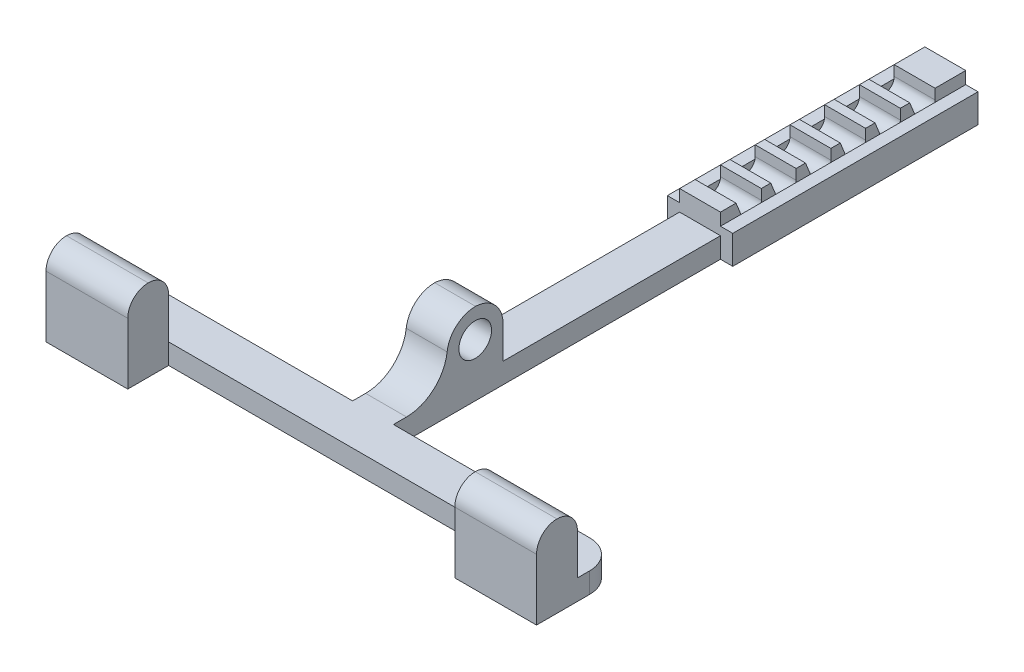
SolidWorks part; units mm, degrees
ref_plane "Front Plane" through (0, 0, 0) normal (0, 0, 1) x (1, 0, 0)
ref_plane "Top Plane" through (0, 0, 0) normal (0, 1, 0) x (1, 0, 0)
ref_plane "Right Plane" through (0, 0, 0) normal (1, 0, 0) x (0, 0, -1)
sketch "Sketch1" plane through (0, 0, 0) normal (0, 1, 0) x (1, 0, 0)
  line L0 (44.6675, -8.5158) -> (60, -8.5158)
  line L1 (0, 0) -> (0, 73.7509) construction
  line L2 (-5, 1.4842) -> (5, 1.4842)
  line L3 (-5, 1.4842) -> (5, 1.4842) construction
  line L4 (-5, 1.4842) -> (-5, 141.4842)
  line L5 (-5, 141.4842) -> (5, 141.4842)
  line L6 (5, 1.4842) -> (5, 141.4842)
  line L7 (-60, -8.5158) -> (44.6675, -8.5158)
  line L8 (-60, -8.5158) -> (-60, 1.4842)
  line L9 (-60, 1.4842) -> (60, 1.4842)
  line L10 (60, -8.5158) -> (60, 1.4842)
  line L11 (-60, -8.5158) -> (60, 1.4842) construction
  line L12 (-60, 1.4842) -> (60, -8.5158) construction
  line L13 (60, -8.5158) -> (40, -8.5158)
  line L14 (60, -8.5158) -> (60, -18.5158)
  line L15 (60, -18.5158) -> (40, -18.5158)
  line L16 (40, -8.5158) -> (40, -18.5158)
  line L17 (-60, -8.5158) -> (-40, -8.5158)
  line L18 (-60, -8.5158) -> (-60, -18.5158)
  line L19 (-60, -18.5158) -> (-40, -18.5158)
  line L20 (-40, -8.5158) -> (-40, -18.5158)
  line L21 (0, -55) -> (0, 55) construction
  line L22 (-5, 81.4842) -> (5, 81.4842)
  line L23 (-5, 28.2887) -> (5, 28.2887)
  line L24 (-5, 28.2887) -> (-5, 14.6797)
  line L25 (-5, 14.6797) -> (5, 14.6797)
  line L26 (5, 28.2887) -> (5, 14.6797)
  line L27 (-5, 28.2887) -> (5, 14.6797) construction
  line L28 (-5, 14.6797) -> (5, 28.2887) construction
  line L29 (5, 141.4842) -> (8, 141.4842)
  line L30 (5, 141.4842) -> (5, 81.4842)
  line L31 (5, 81.4842) -> (8, 81.4842)
  line L32 (8, 141.4842) -> (8, 81.4842)
  line L33 (-5, 141.4842) -> (-8, 141.4842)
  line L34 (-5, 141.4842) -> (-5, 81.4842)
  line L35 (-5, 81.4842) -> (-8, 81.4842)
  line L36 (-8, 141.4842) -> (-8, 81.4842)
  point P0 (0, 0)
  point P5 (0, 21.4842)
  point P6 (0, -3.5158)
  dimension "D1" = 10
  dimension "D2" = 120
  dimension "D3" = 30
  dimension "D4" = 20
  dimension "D5" = 120
  dimension "D6" = 3
  dimension "D7" = 60
extrude "Boss-Extrude1" add sketch "Sketch1" along normal blind 5 contours L7 L16 L15 L14 L0 | L0 L10 L9 L2 L8 L7 | L20 L7 L18 L19 | L25 L4 L2 L6 | L4 L25 L6 L23 | L4 L23 L6 L5 | L4 L23 L6 L22 region at (0, 0, 3.5158) region at (50, 0, 13.5158) region at (-50, 0, 13.5158) region at (0, 0, -8.082) region at (0, 0, -21.4842) region at (0, 0, -54.8865) region at (0, 0, -111.4842)
extrude "Boss-Extrude2" add sketch "Sketch1<3>" along normal blind 20 contours L20 L7 L18 L19 | L7 L16 L15 L14 L0 | L4 L25 L6 L23 region at (50, 0, 13.5158) region at (-50, 0, 13.5158) region at (0, 0, -21.4842)
sketch "Sketch1<3>" plane through (0, 0, 0) normal (0, 1, 0) x (1, 0, 0) same geometry as "Sketch1"
extrude "Boss-Extrude3" add sketch "Sketch1<5>" along normal blind 10 contours L4 L23 L6 L5 region at (0, 0, -111.4842)
sketch "Sketch1<5>" plane through (0, 0, 0) normal (0, 1, 0) x (1, 0, 0) same geometry as "Sketch1"
sketch "Sketch3" plane through (5, 0, 0) normal (1, 0, 0) x (0, 0, -1)
  line L0 (120.6636, 6.5701) -> (119.2891, 10)
  line L1 (81.4842, 10) -> (141.4842, 10) construction
  line L2 (133.9842, 7.5) -> (133.9842, 10)
  line L3 (129.1636, 6.5701) -> (127.7891, 10)
  line L4 (127.7891, 10) -> (133.9842, 10)
  line L5 (141.4842, 6) -> (139.9842, 4.5)
  line L6 (141.4842, 10) -> (141.4842, 0) construction
  line L7 (119.2891, 10) -> (125.4842, 10)
  line L8 (125.4842, 7.5) -> (125.4842, 10)
  line L9 (120.6636, 6.5701) -> (125.4842, 7.5) construction
  line L10 (112.1636, 6.5701) -> (110.7891, 10)
  line L11 (110.7891, 10) -> (116.9842, 10)
  line L12 (116.9842, 7.5) -> (116.9842, 10)
  line L13 (112.1636, 6.5701) -> (116.9842, 7.5) construction
  line L14 (103.6636, 6.5701) -> (102.2891, 10)
  line L15 (102.2891, 10) -> (108.4842, 10)
  line L16 (108.4842, 7.5) -> (108.4842, 10)
  line L17 (103.6636, 6.5701) -> (108.4842, 7.5) construction
  line L18 (95.1636, 6.5701) -> (93.7891, 10)
  line L19 (93.7891, 10) -> (99.9842, 10)
  line L20 (99.9842, 7.5) -> (99.9842, 10)
  line L21 (95.1636, 6.5701) -> (99.9842, 7.5) construction
  line L22 (86.6636, 6.5701) -> (85.2891, 10)
  line L23 (85.2891, 10) -> (91.4842, 10)
  line L24 (91.4842, 7.5) -> (91.4842, 10)
  line L25 (86.6636, 6.5701) -> (91.4842, 7.5) construction
  line L26 (139.9842, 4.5) -> (141.4842, 3)
  line L27 (141.4842, 3) -> (141.4842, 6)
  line L42 (21.4842, 20) -> (21.4842, 5.7881) construction
  line L43 (14.6797, 20) -> (28.2887, 20) construction
  line L44 (28.2887, 13) -> (14.6797, 13) construction
  arc A0 (129.1636, 6.5701) -> (133.9842, 7.5) centre (131.4842, 7.5) ccw
  arc A1 (120.6636, 6.5701) -> (125.4842, 7.5) centre (122.9842, 7.5) ccw
  arc A2 (112.1636, 6.5701) -> (116.9842, 7.5) centre (114.4842, 7.5) ccw
  arc A3 (103.6636, 6.5701) -> (108.4842, 7.5) centre (105.9842, 7.5) ccw
  arc A4 (95.1636, 6.5701) -> (99.9842, 7.5) centre (97.4842, 7.5) ccw
  arc A5 (86.6636, 6.5701) -> (91.4842, 7.5) centre (88.9842, 7.5) ccw
  circle A9 centre (21.4842, 13) radius 4
  dimension "D1" = 10
  dimension "D3" = 2.5
  dimension "D5" = 8
  dimension "D6" = 7
  dimension "D2" = 2.5
  dimension "D7" = 1.5
  dimension "D8" = 4
  dimension "D4" = 6
extrude "Cut-Extrude1" cut sketch "Sketch3" against normal blind 10
fillet "Fillet1" radius 10 1 edges at (0, 5, -14.6797)
fillet "Fillet2" radius 5 4 edges at (-50, 20, 8.5158) (-50, 20, 18.5158) (50, 20, 8.5158) (50, 20, 18.5158)
fillet "Fillet3" radius 7 1 edges at (0, 20, -14.6797)
fillet "Fillet4" radius 7 1 edges at (0, 20, -28.2887)
fillet "Fillet5" radius 7 2 edges at (-60, 2.5, -1.4842) (60, 2.5, -1.4842)
extrude "Boss-Extrude4" add sketch "Sketch1<6>" along normal blind 7 contours L33 L36 L35 L4 | L29 L32 L31 L30 region at (-6.5, 0, -111.4842)
sketch "Sketch1<6>" plane through (0, 0, 0) normal (0, 1, 0) x (1, 0, 0) same geometry as "Sketch1"
